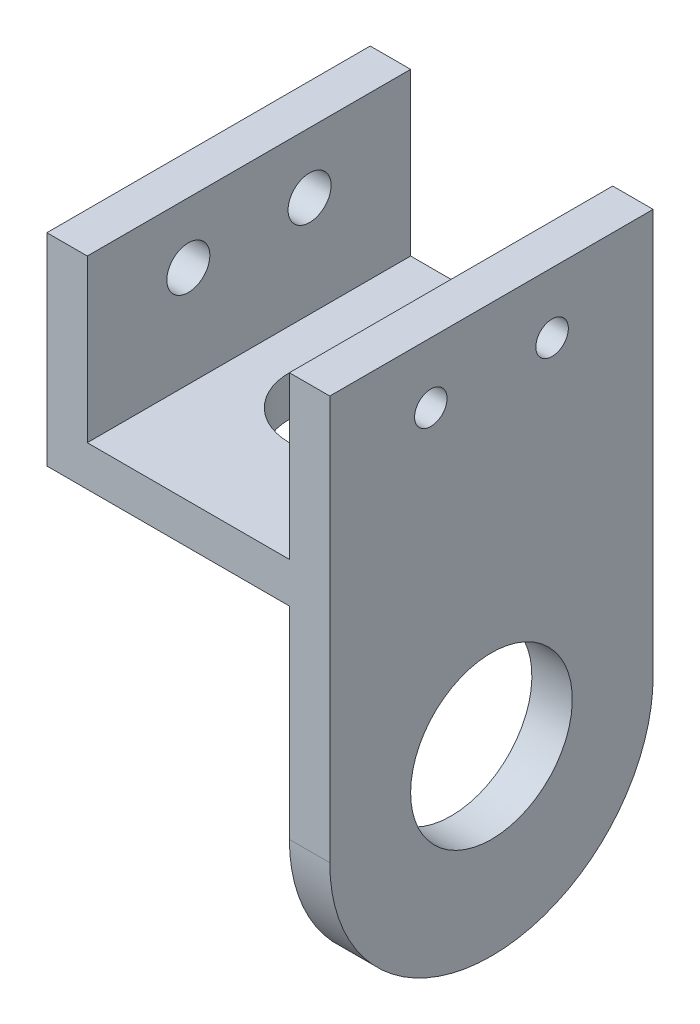
SolidWorks part; units mm, degrees
material "Nylon 101"
ref_plane "Front" through (0, 0, 0) normal (0, 0, 1) x (1, 0, 0)
ref_plane "Top" through (0, 0, 0) normal (0, 1, 0) x (1, 0, 0)
ref_plane "Right" through (0, 0, 0) normal (1, 0, 0) x (0, 0, -1)
sketch "Sketch1" plane through (0, 0, 0) normal (0, 0, 1) x (1, 0, 0)
  line L0 (0, 0) -> (6.35, 0)
  line L1 (6.35, 0) -> (6.35, 88.9)
  line L2 (6.35, 88.9) -> (0, 88.9)
  line L3 (0, 88.9) -> (0, 63.5)
  line L4 (0, 63.5) -> (-31.75, 63.5)
  line L5 (-31.75, 63.5) -> (-31.75, 88.9)
  line L6 (-31.75, 88.9) -> (-38.1, 88.9)
  line L7 (-38.1, 88.9) -> (-38.1, 57.15)
  line L8 (-38.1, 57.15) -> (0, 57.15)
  line L9 (0, 57.15) -> (0, 0)
  point P3 (0, 28.575)
  dimension "D1" = 6.35
  dimension "D2" = 28.575
  dimension "D3" = 31.75
  dimension "D4" = 6.35
  dimension "D5" = 6.35
  dimension "D6" = 25.4
  dimension "D8" = 6.35
extrude "Boss-Extrude1" add sketch "Sketch1" along normal blind 50.8
sketch "Sketch2" plane through (0, 0, 0) normal (-1, 0, 0) x (0, 0, 1)
  line L1 (50.8, 57.15) -> (50.8, 0) construction
  line L2 (50.8, 28.575) -> (0, 28.575) construction
  line L3 (0, 57.15) -> (0, 0) construction
  circle A0 centre (25.4, 28.575) radius 12.7
  point P8 (0, 0)
  point P9 (0, 0)
  point P10 (25.4, 28.575)
  dimension "D3" = 25.4
extrude "Cut-Extrude1" cut sketch "Sketch2" against normal blind 44.45
hole_wizard "1/4-20 Tapped Hole1" positions "Sketch3" profile "Sketch4" tap size "1/4-20" standard "ANSI Inch" end condition through all
sketch "Sketch3" plane through (0, 0, 0) normal (-1, 0, 0) x (0, 0, 1)
  line L2 (50.8, 88.9) -> (0, 88.9) construction
  line L3 (0, 88.9) -> (0, 63.5) construction
  point P0 (15.875, 79.375)
  point P2 (34.925, 79.375)
  dimension "D1" = 19.05
  dimension "D2" = 9.525
  dimension "D3" = 15.875
sketch "Sketch4" plane through (0, 79.375, 15.875) normal (0, 1, 0) x (0, 0, 1)
  line L0 (0, 0) -> (0, 6.35)
  line L1 (0, 6.35) -> (2.5527, 6.35)
  line L2 (2.5527, 6.35) -> (2.5527, 0)
  line L5 (2.5527, 0) -> (0, 0)
  line L11 (0, -6.35) -> (0, 107.95) construction
  dimension "Thru Tap Drill Dia." = 5.1054
  dimension "Thru Tap Drill Depth" = 6.35
cosmetic thread "Hole Thread1" parameters "D2"=6.35
cosmetic thread "Hole Thread2" parameters "D2"=6.35
sketch "Sketch5" plane through (-38.1, 0, 0) normal (-1, 0, 0) x (0, 0, 1)
  line L0 (50.8, 88.9) -> (0, 88.9) construction
  line L1 (50.8, 88.9) -> (50.8, 57.15) construction
  circle A0 centre (15.875, 79.375) radius 3.3782
  circle A1 centre (34.925, 79.375) radius 3.3782
  dimension "D4" = 6.7564
  dimension "D1" = 19.05
  dimension "D2" = 9.525
  dimension "D3" = 15.875
extrude "Cut-Extrude2" cut sketch "Sketch5" against normal blind 8.89
sketch "Sketch6" plane through (0, 63.5, 0) normal (0, 1, 0) x (1, 0, 0)
  line L0 (6.35, -50.8) -> (0, -50.8) construction
  line L2 (0, -50.8) -> (0, 0) construction
  circle A0 centre (-15.875, -25.4) radius 9.525
  dimension "D1" = 19.05
  dimension "D2" = 25.4
  dimension "D3" = 15.875
extrude "Cut-Extrude3" cut sketch "Sketch6" against normal blind 8.89
fillet "Fillet1" 2 edges at (3.175, 0, 50.8) (3.175, 0, 0) type full round first side face at (-12.7, 59.69, 50.8) second side face at (-12.7, 59.69, 0) middle face at (3.175, 0, 25.4)
